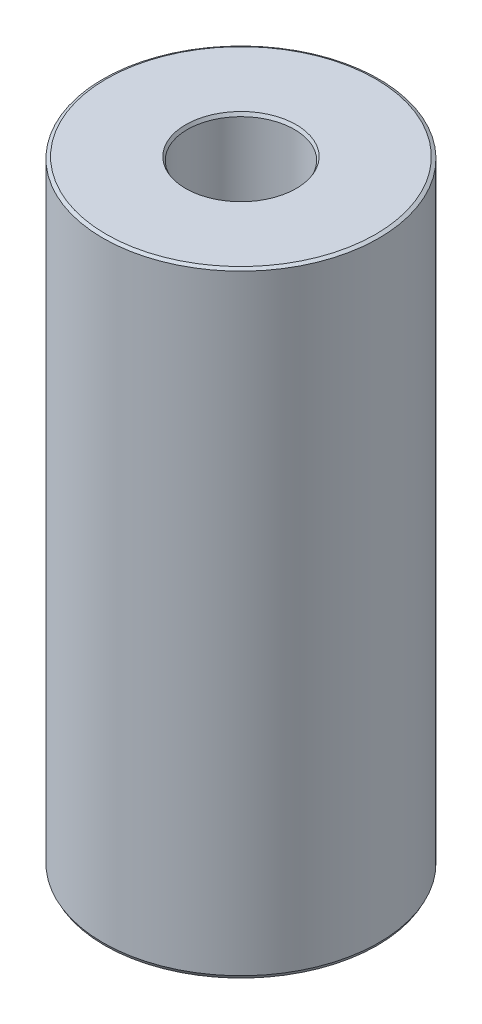
SolidWorks part; units mm, degrees
ref_plane "Front Plane" through (0, 0, 0) normal (0, 0, 1) x (1, 0, 0)
ref_plane "Top Plane" through (0, 0, 0) normal (0, 1, 0) x (1, 0, 0)
ref_plane "Right Plane" through (0, 0, 0) normal (1, 0, 0) x (0, 0, -1)
sketch "Sketch1" plane through (0, 0, 0) normal (0, 1, 0) x (1, 0, 0)
  circle A0 centre (0, 0) radius 47.5
  dimension "SLEEVE_OD" = 95
extrude "Boss-Extrude1" add sketch "Sketch1" along normal blind 211.8637
sketch "Sketch2" plane through (0, 0, 0) normal (0, 1, 0) x (1, 0, 0)
  circle A0 centre (0, 0) radius 18.456
  dimension "BORE_D" = 36.912
extrude "Cut-Extrude1" cut sketch "Sketch2" along normal through all
chamfer "Chamfer1" distance 0.5925 angle 62.222 4 edges at (0, 211.8637, 18.456) (0, 0, 18.456) (0, 0, 47.5) (0, 211.8637, 47.5) first distance on face at (0, 211.8637, 18.456) first distance on face at (0, 0, 18.456) first distance on face at (0, 211.8637, 47.5)
